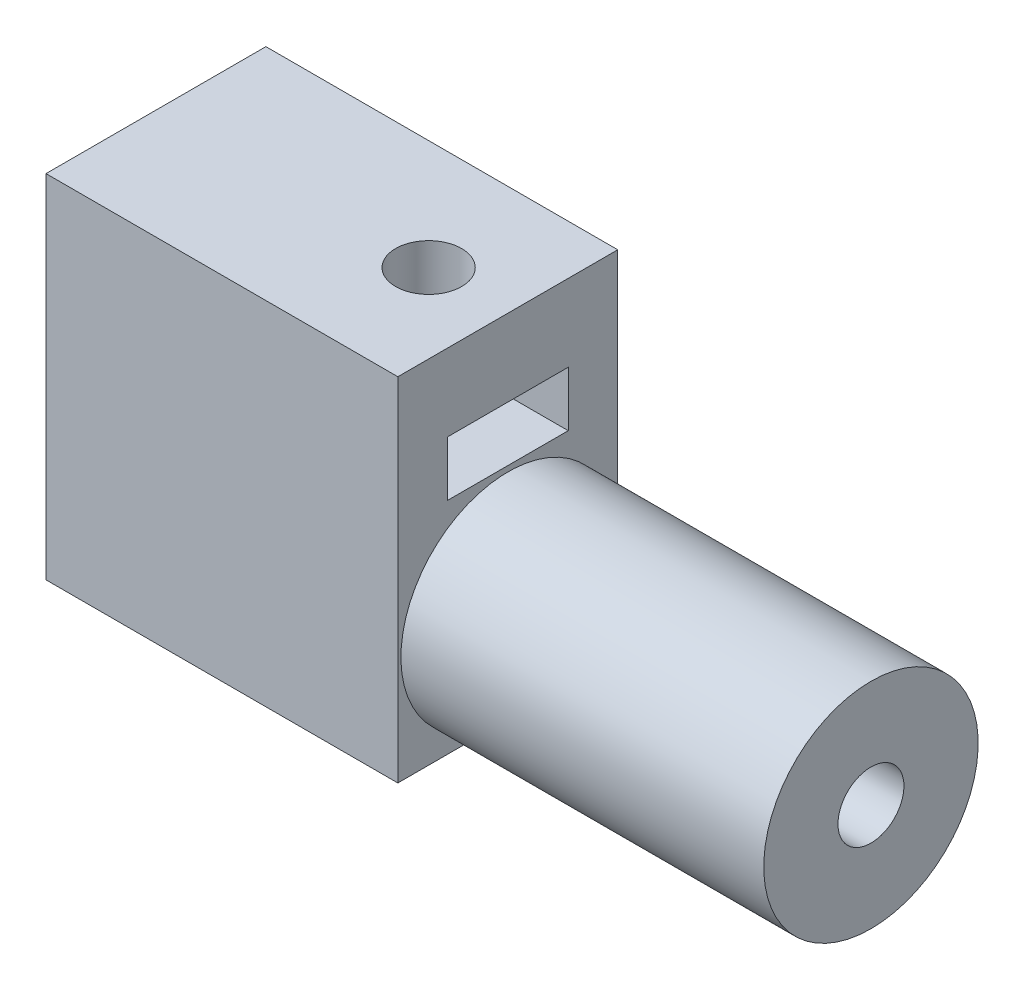
SolidWorks part; units mm, degrees
ref_plane "Front Plane" through (0, 0, 0) normal (0, 0, 1) x (1, 0, 0)
ref_plane "Top Plane" through (0, 0, 0) normal (0, 1, 0) x (1, 0, 0)
ref_plane "Right Plane" through (0, 0, 0) normal (1, 0, 0) x (0, 0, -1)
sketch "Sketch1" plane through (0, 0, 0) normal (0, 0, 1) x (1, 0, 0)
  line L1 (-8, 8) -> (8, 8)
  line L2 (-8, 8) -> (-8, -8)
  line L3 (-8, -8) -> (8, -8)
  line L4 (8, 8) -> (8, -8)
  line L5 (-8, 8) -> (8, -8) construction
  line L6 (-8, -8) -> (8, 8) construction
  point P0 (0, 0)
  dimension "D1" = 16
  dimension "D2" = 16
extrude "Boss-Extrude1" add sketch "Sketch1" along normal blind 10
sketch "Sketch2" plane through (-8, 0, 0) normal (-1, 0, 0) x (0, 0, 1)
  line L0 (10, -8) -> (0, -8) construction
  line L1 (10, 8) -> (0, 8) construction
  circle A0 centre (5, -3.97) radius 1.5
  point P6 (5, -8)
  point P8 (5.4408, 8)
  dimension "D1" = 3
  dimension "D3" = 11.97
  dimension "D2" = 0
extrude "Cut-Extrude1" cut sketch "Sketch2" against normal blind 6
sketch "Sketch3" plane through (0, 8, 0) normal (0, 1, 0) x (1, 0, 0)
  line L0 (8, -10) -> (8, 0) construction
  line L1 (-8, -10) -> (-8, 0) construction
  circle A0 centre (4.4, -5) radius 1.5
  point P6 (8, -5)
  point P8 (8, -6.0134)
  dimension "D3" = 3
  dimension "D1" = 0
  dimension "D2" = 12.4
extrude "Cut-Extrude2" cut sketch "Sketch3" against normal blind 6
sketch "Sketch4" plane through (-8, 0, 0) normal (-1, 0, 0) x (0, 0, 1)
  line L1 (7.75, -2.3823) -> (5, -0.7946)
  line L2 (5, -0.7946) -> (2.25, -2.3823)
  line L3 (2.25, -2.3823) -> (2.25, -5.5577)
  line L4 (2.25, -5.5577) -> (5, -7.1454)
  line L5 (5, -7.1454) -> (7.75, -5.5577)
  line L6 (7.75, -5.5577) -> (7.75, -2.3823)
  circle A0 centre (5, -3.97) radius 2.75 construction
  dimension "D1" = 5.5
extrude "Cut-Extrude3" cut sketch "Sketch4" against normal blind 2.5 from offset 3.5 offset against normal yes
sketch "Sketch6" plane through (-8, 0, 0) normal (-1, 0, 0) x (0, 0, 1)
  line L0 (10, -8) -> (0, -8) construction
  line L1 (2.25, -12.03) -> (7.75, -12.03)
  line L2 (2.25, -12.03) -> (2.25, -3.97)
  line L3 (2.25, -3.97) -> (7.75, -3.97)
  line L4 (7.75, -12.03) -> (7.75, -3.97)
  line L5 (2.25, -12.03) -> (7.75, -3.97) construction
  line L6 (2.25, -3.97) -> (7.75, -12.03) construction
  circle A0 centre (5, -3.97) radius 1.5 construction
  point P0 (5, -8)
  dimension "D1" = 2.75
  dimension "D2" = 0
extrude "Cut-Extrude5" cut sketch "Sketch6" against normal blind 2.5 from offset 3.5 offset against normal yes
sketch "Sketch7" plane through (0, 8, 0) normal (0, 1, 0) x (1, 0, 0)
  line L0 (8, -10) -> (8, 0) construction
  line L1 (7.5747, -5.0699) -> (6.0479, -2.2856)
  line L2 (6.0479, -2.2856) -> (2.8732, -2.2157)
  line L3 (2.8732, -2.2157) -> (1.2253, -4.9301)
  line L4 (1.2253, -4.9301) -> (2.7521, -7.7144)
  line L5 (2.7521, -7.7144) -> (5.9268, -7.7843)
  line L6 (5.9268, -7.7843) -> (7.5747, -5.0699)
  line L8 (11.5395, -7.7493) -> (4.4605, -7.7493)
  line L9 (11.5395, -7.7493) -> (11.5395, -2.2507)
  line L10 (11.5395, -2.2507) -> (4.4605, -2.2507)
  line L11 (4.4605, -7.7493) -> (4.4605, -2.2507)
  line L12 (11.5395, -7.7493) -> (4.4605, -2.2507) construction
  line L13 (11.5395, -2.2507) -> (4.4605, -7.7493) construction
  circle A0 centre (4.4, -5) radius 2.75 construction
  point P11 (8, -5)
  circle M1 centre (4.4, -5) radius 1.5
  line M5 (8, -10) -> (8, 0)
  dimension "D1" = 5.5
extrude "Cut-Extrude6" cut sketch "Sketch7" against normal blind 2.5 from offset 3.5 contours L10 L1 L6 L8 M5 | L11 L5 L6 L1 L2 M1 | L5 L11 L2 L3 L4 M1 | L9 L10 L8 M5 region at (6.7073, 8, 6.3768) region at (6.8686, 8, 3.6463) region at (5.9312, 8, 7.763) region at (9.7697, 8, 5) offset against normal yes
sketch "Sketch9" plane through (8, 0, 0) normal (1, 0, 0) x (0, 0, -1)
  line L0 (-10, -8) -> (0, -8) construction
  circle A0 centre (-4.9855, -3.125) radius 4.875
  dimension "D1" = 9.75
  dimension "D2" = 4.875
extrude "Boss-Extrude2" add sketch "Sketch9" along normal blind 16.5
sketch "Sketch10" plane through (24.5, 0, 0) normal (1, 0, 0) x (0, 0, -1)
  circle A0 centre (-4.9855, -3.125) radius 1.5
  dimension "D1" = 3
extrude "Cut-Extrude7" cut sketch "Sketch10" against normal blind 6
sketch "Sketch11" plane through (24.5, 0, 0) normal (1, 0, 0) x (0, 0, -1)
  line L1 (-4.9855, 0.0504) -> (-7.7355, -1.5373)
  line L2 (-7.7355, -1.5373) -> (-7.7355, -4.7127)
  line L3 (-7.7355, -4.7127) -> (-4.9855, -6.3004)
  line L4 (-4.9855, -6.3004) -> (-2.2355, -4.7127)
  line L5 (-2.2355, -4.7127) -> (-2.2355, -1.5373)
  line L6 (-2.2355, -1.5373) -> (-4.9855, 0.0504)
  line L7 (-7.7355, -12.875) -> (-2.2355, -12.875)
  line L8 (-7.7355, -12.875) -> (-7.7355, -3.125)
  line L9 (-7.7355, -3.125) -> (-2.2355, -3.125)
  line L10 (-2.2355, -12.875) -> (-2.2355, -3.125)
  line L11 (-7.7355, -12.875) -> (-2.2355, -3.125) construction
  line L12 (-7.7355, -3.125) -> (-2.2355, -12.875) construction
  circle A0 centre (-4.9855, -3.125) radius 2.75 construction
  circle A1 centre (-4.9855, -3.125) radius 4.875 construction
  point P1 (-4.9855, -8)
  dimension "D1" = 5.5
extrude "Cut-Extrude9" cut sketch "Sketch11" against normal blind 2.5 from offset 3.5 contours L7 L10 L2 L8 | L2 L10 L4 L3 L8 | L9 L2 L3 L4 L5 L1 | L2 L9 L1 L5 L6 region at (24.5, -1.8901, 4.9855) region at (24.5, -4.3599, 4.9855) region at (24.5, -9.1765, 4.9855) offset against normal yes
